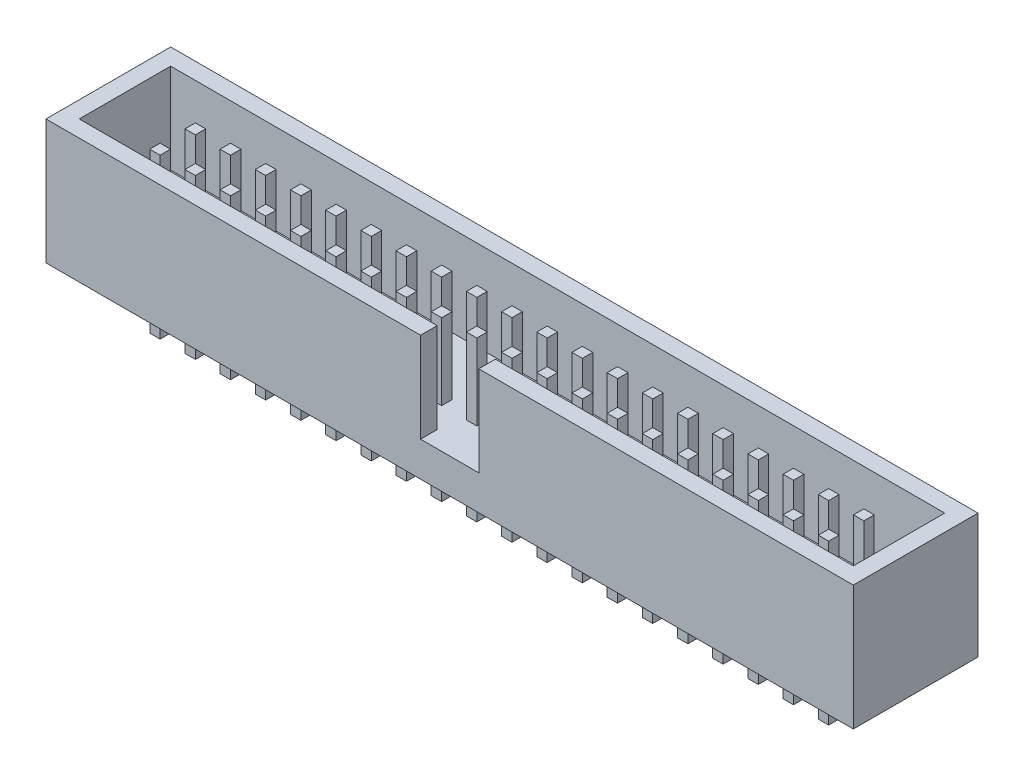
SolidWorks part; units mm, degrees
ref_plane "前视基准面" through (0, 0, 0) normal (0, 0, 1) x (1, 0, 0)
ref_plane "上视基准面" through (0, 0, 0) normal (0, 1, 0) x (1, 0, 0)
ref_plane "右视基准面" through (0, 0, 0) normal (1, 0, 0) x (0, 0, -1)
sketch "草图1" plane through (0, 0, 0) normal (0, 1, 0) x (1, 0, 0)
  line L0 (0, 85.0964) -> (0, -118.2031) construction
  line L1 (-29.14, 4.5) -> (29.14, 4.5)
  line L2 (-29.14, 4.5) -> (-29.14, -4.5)
  line L3 (-29.14, -4.5) -> (29.14, -4.5)
  line L4 (29.14, 4.5) -> (29.14, -4.5)
  line L5 (-200.5452, 0) -> (261.2352, 0) construction
  dimension "D1" = 9
  dimension "D2" = 58.28
extrude "拉伸1" add sketch "草图1" along normal blind 9
sketch "草图2" plane through (0, 9, 0) normal (0, 1, 0) x (-1, 0, 0)
  line L8 (-27.94, 3.3) -> (-27.94, -3.3)
  line L9 (27.94, 3.3) -> (-27.94, 3.3)
  line L10 (27.94, -3.3) -> (27.94, 3.3)
  line L11 (-27.94, -3.3) -> (27.94, -3.3)
  line L12 (-27.94, 3.3) -> (-27.94, -3.3)
  line L13 (27.94, 3.3) -> (-27.94, 3.3)
  line L14 (27.94, -3.3) -> (27.94, 3.3)
  line L15 (-27.94, -3.3) -> (27.94, -3.3)
  dimension "D1" = 1.2
extrude "切除-拉伸1" cut sketch "草图2" against normal blind 6.5
sketch "草图3" plane through (0, 0, 4.5) normal (0, 0, 1) x (1, 0, 0)
  line L0 (-29.14, 9) -> (29.14, 9) construction
  line L1 (-2.1, 9) -> (2.1, 9)
  line L2 (-2.1, 9) -> (-2.1, 2.5)
  line L3 (-2.1, 2.5) -> (2.1, 2.5)
  line L4 (2.1, 9) -> (2.1, 2.5)
  line L5 (-27.94, 2.5) -> (27.94, 2.5) construction
  line L6 (0, 9.4226) -> (0, -4.0288) construction
  dimension "D1" = 4.2
extrude "切除-拉伸2" cut sketch "草图3" against normal blind 6.5
sketch "草图5" plane through (0, 0, 0) normal (0, -1, 0) x (1, 0, 0)
  line L0 (0, 6.0683) -> (0, -6.9786) construction
  line L1 (-14.7999, 0) -> (15.2382, 0) construction
  line L2 (-1.27, 2.5244) -> (-1.27, -0.4442) construction
  line L3 (-1.645, 0.895) -> (-0.895, 0.895)
  line L4 (-1.645, 0.895) -> (-1.645, 1.645)
  line L5 (-1.645, 1.645) -> (-0.895, 1.645)
  line L6 (-0.895, 0.895) -> (-0.895, 1.645)
  line L7 (-2.3518, 1.27) -> (0.5396, 1.27) construction
  line L8 (-4.185, 0.895) -> (-3.435, 0.895)
  line L9 (-4.185, 0.895) -> (-4.185, 1.645)
  line L10 (-4.185, 1.645) -> (-3.435, 1.645)
  line L11 (-3.435, 0.895) -> (-3.435, 1.645)
  line L12 (-6.725, 0.895) -> (-5.975, 0.895)
  line L13 (-6.725, 0.895) -> (-6.725, 1.645)
  line L14 (-6.725, 1.645) -> (-5.975, 1.645)
  line L15 (-5.975, 0.895) -> (-5.975, 1.645)
  line L16 (-9.265, 0.895) -> (-8.515, 0.895)
  line L17 (-9.265, 0.895) -> (-9.265, 1.645)
  line L18 (-9.265, 1.645) -> (-8.515, 1.645)
  line L19 (-8.515, 0.895) -> (-8.515, 1.645)
  line L20 (-8.515, -0.895) -> (-8.515, -1.645)
  line L21 (-9.265, -1.645) -> (-8.515, -1.645)
  line L22 (-9.265, -0.895) -> (-9.265, -1.645)
  line L23 (-9.265, -0.895) -> (-8.515, -0.895)
  line L24 (-5.975, -0.895) -> (-5.975, -1.645)
  line L25 (-6.725, -1.645) -> (-5.975, -1.645)
  line L26 (-6.725, -0.895) -> (-6.725, -1.645)
  line L27 (-6.725, -0.895) -> (-5.975, -0.895)
  line L28 (-3.435, -0.895) -> (-3.435, -1.645)
  line L29 (-4.185, -1.645) -> (-3.435, -1.645)
  line L30 (-4.185, -0.895) -> (-4.185, -1.645)
  line L31 (-4.185, -0.895) -> (-3.435, -0.895)
  line L32 (-0.895, -0.895) -> (-0.895, -1.645)
  line L33 (-1.645, -1.645) -> (-0.895, -1.645)
  line L34 (-1.645, -0.895) -> (-1.645, -1.645)
  line L35 (-1.645, -0.895) -> (-0.895, -0.895)
  line L36 (1.27, 2.5244) -> (1.27, -0.4442) construction
  line L37 (1.645, -0.895) -> (0.895, -0.895)
  line L38 (1.645, -0.895) -> (1.645, -1.645)
  line L39 (1.645, -1.645) -> (0.895, -1.645)
  line L40 (0.895, -0.895) -> (0.895, -1.645)
  line L41 (4.185, -0.895) -> (3.435, -0.895)
  line L42 (4.185, -0.895) -> (4.185, -1.645)
  line L43 (4.185, -1.645) -> (3.435, -1.645)
  line L44 (3.435, -0.895) -> (3.435, -1.645)
  line L45 (6.725, -0.895) -> (5.975, -0.895)
  line L46 (6.725, -0.895) -> (6.725, -1.645)
  line L47 (6.725, -1.645) -> (5.975, -1.645)
  line L48 (5.975, -0.895) -> (5.975, -1.645)
  line L49 (9.265, -0.895) -> (8.515, -0.895)
  line L50 (9.265, -0.895) -> (9.265, -1.645)
  line L51 (9.265, -1.645) -> (8.515, -1.645)
  line L52 (8.515, -0.895) -> (8.515, -1.645)
  line L53 (8.515, 0.895) -> (8.515, 1.645)
  line L54 (9.265, 1.645) -> (8.515, 1.645)
  line L55 (9.265, 0.895) -> (9.265, 1.645)
  line L56 (9.265, 0.895) -> (8.515, 0.895)
  line L57 (5.975, 0.895) -> (5.975, 1.645)
  line L58 (6.725, 1.645) -> (5.975, 1.645)
  line L59 (6.725, 0.895) -> (6.725, 1.645)
  line L60 (6.725, 0.895) -> (5.975, 0.895)
  line L61 (3.435, 0.895) -> (3.435, 1.645)
  line L62 (4.185, 1.645) -> (3.435, 1.645)
  line L63 (4.185, 0.895) -> (4.185, 1.645)
  line L64 (4.185, 0.895) -> (3.435, 0.895)
  line L65 (0.895, 0.895) -> (0.895, 1.645)
  line L66 (1.645, 1.645) -> (0.895, 1.645)
  line L67 (1.645, 0.895) -> (1.645, 1.645)
  line L68 (1.645, 0.895) -> (0.895, 0.895)
  line L69 (11.805, -0.895) -> (11.055, -0.895)
  line L70 (11.805, -0.895) -> (11.805, -1.645)
  line L71 (11.805, -1.645) -> (11.055, -1.645)
  line L72 (11.055, -0.895) -> (11.055, -1.645)
  line L73 (11.055, 0.895) -> (11.055, 1.645)
  line L74 (11.805, 1.645) -> (11.055, 1.645)
  line L75 (11.805, 0.895) -> (11.805, 1.645)
  line L76 (11.805, 0.895) -> (11.055, 0.895)
  line L77 (14.345, -0.895) -> (13.595, -0.895)
  line L78 (14.345, -0.895) -> (14.345, -1.645)
  line L79 (14.345, -1.645) -> (13.595, -1.645)
  line L80 (13.595, -0.895) -> (13.595, -1.645)
  line L81 (13.595, 0.895) -> (13.595, 1.645)
  line L82 (14.345, 1.645) -> (13.595, 1.645)
  line L83 (14.345, 0.895) -> (14.345, 1.645)
  line L84 (14.345, 0.895) -> (13.595, 0.895)
  line L85 (16.885, -0.895) -> (16.135, -0.895)
  line L86 (16.885, -0.895) -> (16.885, -1.645)
  line L87 (16.885, -1.645) -> (16.135, -1.645)
  line L88 (16.135, -0.895) -> (16.135, -1.645)
  line L89 (16.135, 0.895) -> (16.135, 1.645)
  line L90 (16.885, 1.645) -> (16.135, 1.645)
  line L91 (16.885, 0.895) -> (16.885, 1.645)
  line L92 (16.885, 0.895) -> (16.135, 0.895)
  line L93 (19.425, -0.895) -> (18.675, -0.895)
  line L94 (19.425, -0.895) -> (19.425, -1.645)
  line L95 (19.425, -1.645) -> (18.675, -1.645)
  line L96 (18.675, -0.895) -> (18.675, -1.645)
  line L97 (18.675, 0.895) -> (18.675, 1.645)
  line L98 (19.425, 1.645) -> (18.675, 1.645)
  line L99 (19.425, 0.895) -> (19.425, 1.645)
  line L100 (19.425, 0.895) -> (18.675, 0.895)
  line L101 (21.965, -0.895) -> (21.215, -0.895)
  line L102 (21.965, -0.895) -> (21.965, -1.645)
  line L103 (21.965, -1.645) -> (21.215, -1.645)
  line L104 (21.215, -0.895) -> (21.215, -1.645)
  line L105 (21.215, 0.895) -> (21.215, 1.645)
  line L106 (21.965, 1.645) -> (21.215, 1.645)
  line L107 (21.965, 0.895) -> (21.965, 1.645)
  line L108 (21.965, 0.895) -> (21.215, 0.895)
  line L109 (24.505, -0.895) -> (23.755, -0.895)
  line L110 (24.505, -0.895) -> (24.505, -1.645)
  line L111 (24.505, -1.645) -> (23.755, -1.645)
  line L112 (23.755, -0.895) -> (23.755, -1.645)
  line L113 (23.755, 0.895) -> (23.755, 1.645)
  line L114 (24.505, 1.645) -> (23.755, 1.645)
  line L115 (24.505, 0.895) -> (24.505, 1.645)
  line L116 (24.505, 0.895) -> (23.755, 0.895)
  line L117 (-11.805, 0.895) -> (-11.055, 0.895)
  line L118 (-11.805, 0.895) -> (-11.805, 1.645)
  line L119 (-11.805, 1.645) -> (-11.055, 1.645)
  line L120 (-11.055, 0.895) -> (-11.055, 1.645)
  line L121 (-11.055, -0.895) -> (-11.055, -1.645)
  line L122 (-11.805, -1.645) -> (-11.055, -1.645)
  line L123 (-11.805, -0.895) -> (-11.805, -1.645)
  line L124 (-11.805, -0.895) -> (-11.055, -0.895)
  line L125 (-14.345, 0.895) -> (-13.595, 0.895)
  line L126 (-14.345, 0.895) -> (-14.345, 1.645)
  line L127 (-14.345, 1.645) -> (-13.595, 1.645)
  line L128 (-13.595, 0.895) -> (-13.595, 1.645)
  line L129 (-13.595, -0.895) -> (-13.595, -1.645)
  line L130 (-14.345, -1.645) -> (-13.595, -1.645)
  line L131 (-14.345, -0.895) -> (-14.345, -1.645)
  line L132 (-14.345, -0.895) -> (-13.595, -0.895)
  line L133 (-16.885, 0.895) -> (-16.135, 0.895)
  line L134 (-16.885, 0.895) -> (-16.885, 1.645)
  line L135 (-16.885, 1.645) -> (-16.135, 1.645)
  line L136 (-16.135, 0.895) -> (-16.135, 1.645)
  line L137 (-16.135, -0.895) -> (-16.135, -1.645)
  line L138 (-16.885, -1.645) -> (-16.135, -1.645)
  line L139 (-16.885, -0.895) -> (-16.885, -1.645)
  line L140 (-16.885, -0.895) -> (-16.135, -0.895)
  line L141 (-19.425, 0.895) -> (-18.675, 0.895)
  line L142 (-19.425, 0.895) -> (-19.425, 1.645)
  line L143 (-19.425, 1.645) -> (-18.675, 1.645)
  line L144 (-18.675, 0.895) -> (-18.675, 1.645)
  line L145 (-18.675, -0.895) -> (-18.675, -1.645)
  line L146 (-19.425, -1.645) -> (-18.675, -1.645)
  line L147 (-19.425, -0.895) -> (-19.425, -1.645)
  line L148 (-19.425, -0.895) -> (-18.675, -0.895)
  line L149 (-21.965, 0.895) -> (-21.215, 0.895)
  line L150 (-21.965, 0.895) -> (-21.965, 1.645)
  line L151 (-21.965, 1.645) -> (-21.215, 1.645)
  line L152 (-21.215, 0.895) -> (-21.215, 1.645)
  line L153 (-21.215, -0.895) -> (-21.215, -1.645)
  line L154 (-21.965, -1.645) -> (-21.215, -1.645)
  line L155 (-21.965, -0.895) -> (-21.965, -1.645)
  line L156 (-21.965, -0.895) -> (-21.215, -0.895)
  line L157 (-24.505, 0.895) -> (-23.755, 0.895)
  line L158 (-24.505, 0.895) -> (-24.505, 1.645)
  line L159 (-24.505, 1.645) -> (-23.755, 1.645)
  line L160 (-23.755, 0.895) -> (-23.755, 1.645)
  line L161 (-23.755, -0.895) -> (-23.755, -1.645)
  line L162 (-24.505, -1.645) -> (-23.755, -1.645)
  line L163 (-24.505, -0.895) -> (-24.505, -1.645)
  line L164 (-24.505, -0.895) -> (-23.755, -0.895)
  dimension "D1" = 0.75
  dimension "D2" = 0.75
  dimension "D3" = 1.27
  dimension "D4" = 1.27
extrude "拉伸2" add sketch "草图5" along normal blind 3.5 and the other way offset from surface 1 other way up to face at (0, 9, 1.3)
sketch "草图6" plane through (0, 0, 0) normal (0, -1, 0) x (1, 0, 0)
  line L0 (34.2898, 0) -> (-33.2336, 0) construction
  line L1 (0, 6.8981) -> (0, -7.2913) construction
  line L10 (24.505, 0.895) -> (24.505, 1.645) construction
  line L11 (24.505, 1.645) -> (23.755, 1.645) construction
  line L13 (23.755, 0.895) -> (24.505, 0.895) construction
  circle A0 centre (24.13, 1.27) radius 0.375
